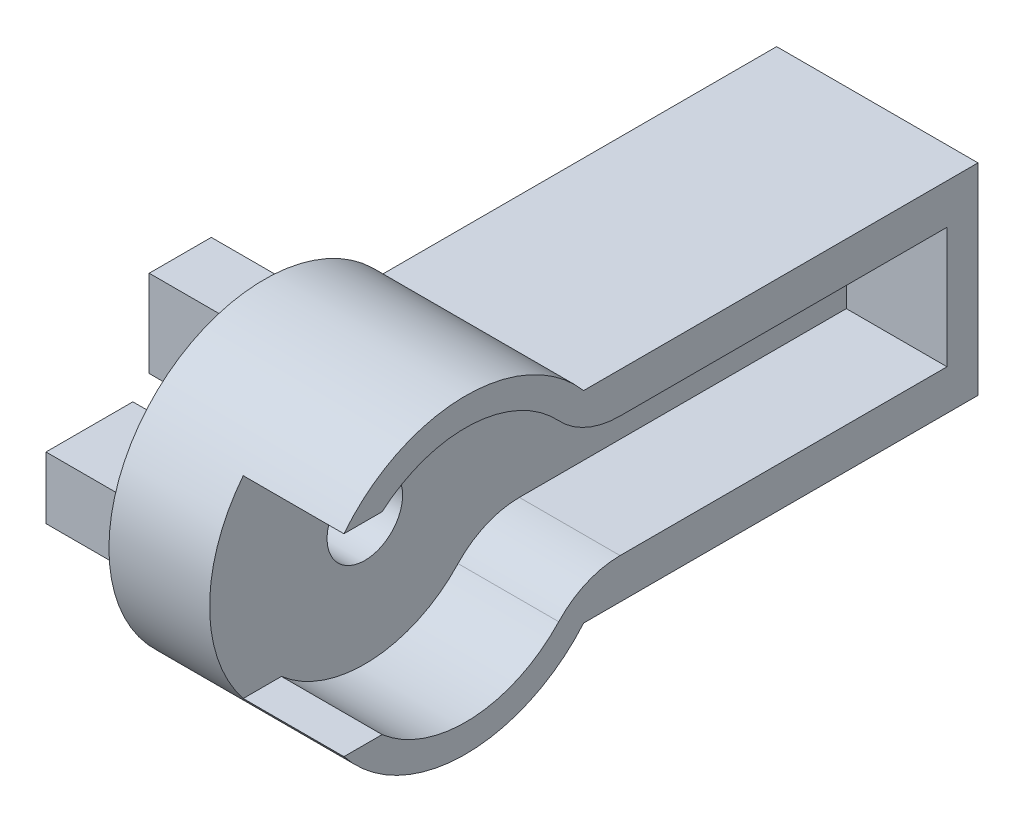
SolidWorks part; units mm, degrees
ref_plane "Front Plane" through (0, 0, 0) normal (0, 0, 1) x (1, 0, 0)
ref_plane "Top Plane" through (0, 0, 0) normal (0, 1, 0) x (1, 0, 0)
ref_plane "Right Plane" through (0, 0, 0) normal (1, 0, 0) x (0, 0, -1)
sketch "Sketch1" plane through (0, 0, 0) normal (1, 0, 0) x (0, 0, -1)
  line L1 (7.0401, 6) -> (30.5401, 6)
  line L2 (7.0401, 6) -> (7.0401, -6)
  line L3 (7.0401, -6) -> (30.5401, -6)
  line L4 (30.5401, 6) -> (30.5401, -6)
  circle A0 centre (0, 0) radius 9.25
  point P7 (8.124, -3.873)
  dimension "D1" = 18.5
  dimension "D2" = 23.5
  dimension "D3" = 12
extrude "Boss-Extrude1" add sketch "Sketch1" along normal blind 12 contours A0 L3 L4 L1 | L2 A0 | L2 L3 L4 L1 region at (0, 0, -19.5369) region at (0, 0, 0.5745)
sketch "Sketch2" plane through (12, 0, 0) normal (1, 0, 0) x (0, 0, -1)
  line L1 (6.6933, 3.6) -> (28.6933, 3.6)
  line L2 (6.6933, 3.6) -> (6.6933, -3.6)
  line L3 (6.6933, -3.6) -> (28.6933, -3.6)
  line L4 (28.6933, 3.6) -> (28.6933, -3.6)
  line L5 (-4.9697, 5.75) -> (-11.0599, 5.75)
  line L6 (-4.9697, 5.75) -> (-4.9697, -5.75)
  line L7 (-4.9697, -5.75) -> (-11.0599, -5.75)
  line L8 (-11.0599, 5.75) -> (-11.0599, -5.75)
  circle A0 centre (0, 0) radius 7.6
  point P7 (-6.1103, -4.5194)
  dimension "D1" = 15.2
  dimension "D2" = 22
  dimension "D3" = 7.2
  dimension "D4" = 11.5
extrude "Cut-Extrude1" cut sketch "Sketch2" against normal blind 6 contours A0 L3 L4 L1 | L2 A0 | L6 L5 L8 L7 | A0 region at (12, 0, -7.0579) region at (12, 0, -17.9976)
fillet "Fillet1" radius 5 2 edges at (9, 3.6, -6.6933) (9, -3.6, -6.6933)
sketch "Sketch3" plane through (6, 0, 0) normal (1, 0, 0) x (0, 0, -1)
  line L0 (0, 0) -> (35.2633, 0) construction
  circle A0 centre (0, 0) radius 2.25
  circle A1 centre (20.5, 0) radius 1.65
  circle A2 centre (24.5, 0) radius 1.65
  dimension "D1" = 4.5
  dimension "D2" = 3.3
  dimension "D3" = 3.3
  dimension "D4" = 20.5
  dimension "D5" = 24.5
extrude "Cut-Extrude2" cut sketch "Sketch3" against normal up to surface (6 mm away) up to face at (0, 0, -14.7175)
sketch "Sketch5" plane through (0, 0, 0) normal (-1, 0, 0) x (0, 0, 1)
  line L9 (-8, 1.85) -> (8, 1.85)
  line L10 (-8, 1.85) -> (-8, -1.85)
  line L11 (-8, -1.85) -> (8, -1.85)
  line L12 (8, 1.85) -> (8, -1.85)
  line L13 (-8, 1.85) -> (8, -1.85) construction
  line L14 (-8, -1.85) -> (8, 1.85) construction
  line L15 (-1.85, 8) -> (1.85, 8)
  line L16 (-1.85, 8) -> (-1.85, -8)
  line L17 (-1.85, -8) -> (1.85, -8)
  line L18 (1.85, 8) -> (1.85, -8)
  line L19 (-1.85, 8) -> (1.85, -8) construction
  line L20 (-1.85, -8) -> (1.85, 8) construction
  point P0 (0, 0)
  point P6 (0, 0)
  circle M12 centre (0, 0) radius 2.25
  dimension "D3" = 16
  dimension "D1" = 3.7
  dimension "D2" = 3.7
  dimension "D4" = 16
extrude "Boss-Extrude2" add sketch "Sketch5" along normal blind 5 contours L16 L9 L10 L11 M12 | L18 L15 L16 L9 M12 | L9 L18 L11 L12 M12 | L18 L11 L16 L17 M12 | L9 L16 M12 | L18 L9 M12 | L18 L11 M12 | L16 L11 M12 region at (0, 0, -5.017) region at (0, 5.017, 0) region at (0, 1.6718, -1.6718) region at (0, -1.6718, -1.6718) region at (0, -5.017, 0) region at (0, 1.6718, 1.6718) region at (0, 0, 5.017) region at (0, -1.6718, 1.6718)
sketch "Sketch6" plane through (-5, 0, 0) normal (-1, 0, 0) x (0, 0, 1)
  circle A0 centre (0, 0) radius 3.375
  dimension "D1" = 6.75
extrude "Cut-Extrude3" cut sketch "Sketch6" against normal up to surface (5 mm away) up to face at (0, 0, 0)
